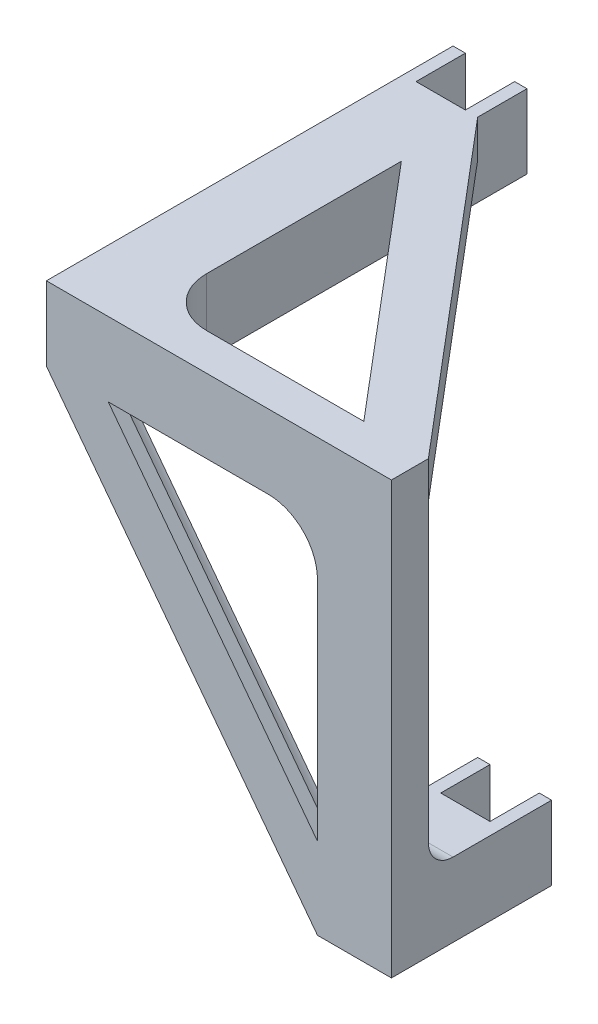
SolidWorks part; units mm, degrees
ref_plane "前视基准面" through (0, 0, 0) normal (0, 0, 1) x (1, 0, 0)
ref_plane "上视基准面" through (0, 0, 0) normal (0, 1, 0) x (1, 0, 0)
ref_plane "右视基准面" through (0, 0, 0) normal (1, 0, 0) x (0, 0, -1)
sketch "草图1" plane through (0, 0, 0) normal (0, 0, 1) x (1, 0, 0)
  line L1 (-70, 87.5) -> (70, 87.5)
  line L2 (-70, 87.5) -> (-70, -87.5)
  line L3 (-70, -87.5) -> (70, -87.5)
  line L4 (70, 87.5) -> (70, -87.5)
  line L5 (-70, 87.5) -> (70, -87.5) construction
  line L6 (-70, -87.5) -> (70, 87.5) construction
  point P0 (0, 0)
  dimension "D1" = 140
  dimension "D2" = 175
extrude "凸台-拉伸1" add sketch "草图1" along normal blind 150
sketch "草图2" plane through (0, 0, 150) normal (0, 0, 1) x (1, 0, 0)
  line L0 (70, -87.5) -> (70, 87.5) construction
  line L1 (-70, -87.5) -> (40, -87.5)
  line L2 (-70, -87.5) -> (-70, 57.5)
  line L3 (-70, 57.5) -> (40, 57.5)
  line L4 (40, -87.5) -> (40, 57.5)
  line L5 (70, 87.5) -> (-70, 87.5) construction
  dimension "D1" = 30
  dimension "D2" = 30
extrude "切除-拉伸1" cut sketch "草图2" against normal blind 150
sketch "草图3" plane through (40, 0, 0) normal (-1, 0, 0) x (0, 0, 1)
  line L0 (0, -87.5) -> (150, -87.5) construction
  line L1 (0, 57.5) -> (115, 57.5)
  line L2 (0, 57.5) -> (0, -87.5)
  line L3 (0, -87.5) -> (115, -87.5)
  line L4 (115, 57.5) -> (115, -87.5)
  line L5 (150, -87.5) -> (150, 57.5) construction
  dimension "D1" = 35
extrude "切除-拉伸2" cut sketch "草图3" against normal blind 150
sketch "草图4" plane through (0, 57.5, 0) normal (0, -1, 0) x (1, 0, 0)
  line L0 (40, 150) -> (-70, 150) construction
  line L1 (70, 0) -> (-40, 0)
  line L2 (70, 0) -> (70, 135)
  line L3 (70, 135) -> (-40, 135)
  line L4 (-40, 0) -> (-40, 135)
  line L5 (-70, 0) -> (-70, 150) construction
  dimension "D1" = 15
  dimension "D2" = 30
extrude "切除-拉伸3" cut sketch "草图4" against normal blind 150
sketch "草图5" plane through (0, -87.5, 0) normal (0, -1, 0) x (1, 0, 0)
  line L0 (70, 115) -> (40, 115) construction
  line L1 (65, 95) -> (45, 95)
  line L2 (65, 95) -> (65, 135)
  line L3 (65, 135) -> (45, 135)
  line L4 (45, 95) -> (45, 135)
  line L5 (65, 95) -> (45, 135) construction
  line L6 (65, 135) -> (45, 95) construction
  point P0 (55, 115)
  dimension "D1" = 20
  dimension "D2" = 40
extrude "切除-拉伸4" cut sketch "草图5" against normal blind 150
sketch "草图6" plane through (40, 0, 0) normal (-1, 0, 0) x (0, 0, 1)
  line L0 (115, -87.5) -> (115, 57.5) construction
  line L1 (115, -57.5) -> (135, -57.5)
  line L2 (115, -57.5) -> (115, 57.5)
  line L3 (115, 57.5) -> (135, 57.5)
  line L4 (135, -57.5) -> (135, 57.5)
  line L5 (0, 57.5) -> (150, 57.5) construction
  line L6 (115, -87.5) -> (150, -87.5) construction
  dimension "D1" = 30
  dimension "D2" = 20
extrude "切除-拉伸5" cut sketch "草图6" against normal blind 150
sketch "草图7" plane through (0, 0, 150) normal (0, 0, 1) x (1, 0, 0)
  line L6 (-70, 57.5) -> (40, 57.5)
  line L7 (40, 57.5) -> (40, -87.5)
  line L8 (40, -87.5) -> (70, -87.5)
  line L9 (70, -87.5) -> (70, 87.5)
  line L10 (70, 87.5) -> (-70, 87.5)
  line L11 (-70, 87.5) -> (-70, 57.5)
  line L12 (-70, 57.5) -> (40, 57.5)
  line L13 (40, 57.5) -> (40, -87.5)
  line L14 (40, -87.5) -> (70, -87.5)
  line L15 (70, -87.5) -> (70, 87.5)
  line L16 (70, 87.5) -> (-70, 87.5)
  line L17 (-70, 87.5) -> (-70, 57.5)
  dimension "D1" = 0
extrude "凸台-拉伸2" add sketch "草图7" along normal blind 30
sketch "草图8" plane through (0, 0, 135) normal (0, 0, -1) x (-1, 0, 0)
  line L0 (-65, -57.5) -> (-45, -57.5)
  line L10 (-40, -57.5) -> (-40, 57.5)
  line L11 (-40, 57.5) -> (40, 57.5)
  line L12 (40, 57.5) -> (40, 87.5)
  line L13 (40, 87.5) -> (-70, 87.5)
  line L14 (-70, 87.5) -> (-70, -57.5)
  line L15 (-70, -57.5) -> (-65, -57.5)
  line L16 (-65, -57.5) -> (-65, -87.5)
  line L17 (-65, -87.5) -> (-45, -87.5)
  line L18 (-45, -87.5) -> (-45, -57.5)
  line L19 (-45, -57.5) -> (-40, -57.5)
  line L20 (-40, -57.5) -> (-40, 57.5)
  line L21 (-40, 57.5) -> (40, 57.5)
  line L22 (40, 57.5) -> (40, 87.5)
  line L23 (40, 87.5) -> (-70, 87.5)
  line L24 (-70, 87.5) -> (-70, -57.5)
  line L25 (-70, -57.5) -> (-65, -57.5)
  line L29 (-45, -57.5) -> (-40, -57.5)
  dimension "D1" = 0
extrude "切除-拉伸6" cut sketch "草图8" against normal blind 30
sketch "草图9" plane through (0, 0, 0) normal (0, 0, -1) x (-1, 0, 0)
  line L4 (70, 87.5) -> (40, 87.5)
  line L5 (40, 87.5) -> (40, 57.5)
  line L6 (40, 57.5) -> (70, 57.5)
  line L7 (70, 57.5) -> (70, 87.5)
  line L8 (70, 87.5) -> (40, 87.5)
  line L9 (40, 87.5) -> (40, 57.5)
  line L10 (40, 57.5) -> (70, 57.5)
  line L11 (70, 57.5) -> (70, 87.5)
  dimension "D1" = 0
extrude "切除-拉伸7" cut sketch "草图9" against normal blind 15
sketch "草图10" plane through (0, 0, 15) normal (0, 0, -1) x (-1, 0, 0)
  line L0 (70, 87.5) -> (40, 87.5) construction
  line L1 (45, 117.5) -> (65, 117.5)
  line L2 (45, 117.5) -> (45, 57.5)
  line L3 (45, 57.5) -> (65, 57.5)
  line L4 (65, 117.5) -> (65, 57.5)
  line L5 (45, 117.5) -> (65, 57.5) construction
  line L6 (45, 57.5) -> (65, 117.5) construction
  line L7 (40, 57.5) -> (70, 57.5) construction
  point P0 (55, 87.5)
  dimension "D1" = 20
extrude "切除-拉伸8" cut sketch "草图10" against normal blind 20
sketch "草图11" plane through (0, 87.5, 0) normal (0, 1, 0) x (1, 0, 0)
  line L0 (-40, -35) -> (70, -165)
  line L1 (-40, -165) -> (-40, -15) construction
  line L2 (-40, -165) -> (70, -165) construction
  line L3 (70, -165) -> (-40, -165)
  line L4 (-40, -165) -> (-40, -35)
  dimension "D1" = 130
  dimension "D2" = 110
extrude "凸台-拉伸3" add sketch "草图11" against normal blind 5
sketch "草图12" plane through (0, 0, 180) normal (0, 0, 1) x (1, 0, 0)
  line L0 (-70, 57.5) -> (40, -87.5)
  line L1 (40, -87.5) -> (40, 57.5)
  line L2 (40, 57.5) -> (-70, 57.5)
extrude "凸台-拉伸4" add sketch "草图12" against normal blind 5
sketch "草图13" plane through (0, 0, 175) normal (0, 0, -1) x (-1, 0, 0)
  line L0 (70, 57.5) -> (-40, -87.5)
extrude "拉伸-薄壁1" add sketch "草图13" along normal blind 10 thin thin type one direction wall 10
sketch "草图14" plane through (0, 82.5, 0) normal (0, -1, 0) x (1, 0, 0)
  line L0 (-40, 35) -> (70, 165)
extrude "拉伸-薄壁2" add sketch "草图14" along normal blind 10 thin thin type one direction reverse wall 10
fillet "圆角1" radius 10 2 edges at (8.4502, 82.5, 107.7406) (-8.724, -6.7271, 175)
sketch "草图15" plane through (0, 0, 175) normal (0, 0, -1) x (-1, 0, 0)
  line L3 (-40, 57.5) -> (-40, -54.4086)
  line L4 (-40, -54.4086) -> (44.8962, 57.5)
  line L5 (44.8962, 57.5) -> (-40, 57.5)
  line L6 (-40, 57.5) -> (-40, -54.4086)
  line L7 (-40, -54.4086) -> (44.8962, 57.5)
  line L8 (44.8962, 57.5) -> (-40, 57.5)
  dimension "D1" = 0
extrude "切除-拉伸9" cut sketch "草图15" against normal blind 52
sketch "草图16" plane through (0, 82.5, 0) normal (0, -1, 0) x (1, 0, 0)
  line L3 (-40, 165) -> (-40, 65.9625)
  line L4 (-40, 65.9625) -> (43.8009, 165)
  line L5 (43.8009, 165) -> (-40, 165)
  line L6 (-40, 165) -> (-40, 65.9625)
  line L7 (-40, 65.9625) -> (43.8009, 165)
  line L8 (43.8009, 165) -> (-40, 165)
  dimension "D1" = 0
extrude "切除-拉伸10" cut sketch "草图16" against normal blind 52
fillet "圆角2" radius 20 2 edges at (40, 57.5, 172.5) (-40, 72.5, 165)
fillet "圆角3" radius 10 1 edges at (55, -57.5, 165)
